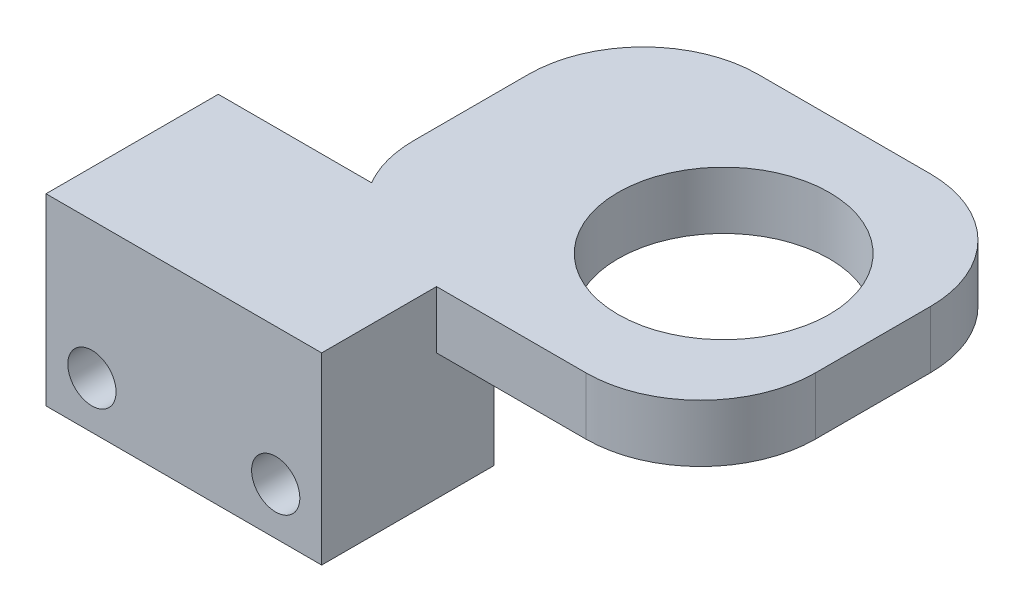
SolidWorks part; units mm, degrees
note: The reader was unsure of these and kept them because the rebuilt part matched: shared geometry of "Skizze1<4>".
ref_plane "Ebene vorne" through (0, 0, 0) normal (0, 0, 1) x (1, 0, 0)
ref_plane "Ebene oben" through (0, 0, 0) normal (0, 1, 0) x (1, 0, 0)
ref_plane "Ebene rechts" through (0, 0, 0) normal (1, 0, 0) x (0, 0, -1)
sketch "Skizze1" plane through (0, 0, 0) normal (0, 0, 1) x (1, 0, 0)
  line L1 (-7.1866, 4.7872) -> (16.8134, 4.7872)
  line L2 (-7.1866, 4.7872) -> (-7.1866, -11.2128)
  line L3 (-7.1866, -11.2128) -> (16.8134, -11.2128)
  line L4 (16.8134, 4.7872) -> (16.8134, -11.2128)
  circle A0 centre (-3.1866, -7.1128) radius 2.1
  circle A1 centre (12.8134, -7.1128) radius 2.1
  dimension "D3" = 4.2
  dimension "D4" = 4.2
  dimension "D6" = 16
  dimension "D7" = 4
  dimension "D8" = 4.1
  dimension "D9" = 4.1
  dimension "D1" = 16
  dimension "D2" = 24
  dimension "D5" = 4
extrude "Aufsatz-Linear austragen2" add sketch "Skizze1" along normal blind 5
sketch "Skizze12" plane through (0, 4.7872, 0) normal (0, 1, 0) x (1, 0, 0)
  line L0 (16.8134, -5) -> (26.8134, -5)
  line L2 (4.8134, 5) -> (4.8134, 15)
  line L3 (14.8134, -5) -> (29.8134, -5)
  line L4 (26.8134, -5) -> (26.8134, 10)
  line L5 (16.8134, -5) -> (21.8134, -5)
  line L6 (14.8134, 25) -> (29.8134, 25)
  line L7 (39.8134, 5) -> (39.8134, 15)
  line L8 (16.8134, -5) -> (-7.1866, -5) construction
  circle A0 centre (26.8134, 10) radius 9.2
  arc A1 (4.8134, 5) -> (14.8134, -5) centre (14.8134, 5) ccw
  arc A2 (39.8134, 5) -> (29.8134, -5) centre (29.8134, 5) cw
  arc A3 (39.8134, 15) -> (29.8134, 25) centre (29.8134, 15) ccw
  arc A4 (14.8134, 25) -> (4.8134, 15) centre (14.8134, 15) ccw
  point P15 (4.8134, -5)
  point P18 (39.8134, -5)
  point P23 (4.8134, 25)
  dimension "D1" = 10
  dimension "D2" = 30
  dimension "D3" = 35
  dimension "D4" = 10
extrude "Aufsatz-Linear austragen6" add sketch "Skizze12" against normal blind 5
sketch "Skizze13" plane through (0, 0, 5) normal (0, 0, 1) x (1, 0, 0)
  line L1 (-7.1866, 4.7872) -> (16.8134, 4.7872)
  line L2 (-7.1866, 4.7872) -> (-7.1866, -11.2128)
  line L3 (-7.1866, -11.2128) -> (16.8134, -11.2128)
  line L4 (16.8134, 4.7872) -> (16.8134, -11.2128)
extrude "Aufsatz-Linear austragen8" add sketch "Skizze1<4>" along normal blind 15
sketch "Skizze1<4>" plane through (0, 0, 0) normal (0, 0, 1) x (1, 0, 0) same geometry as "Skizze1"
